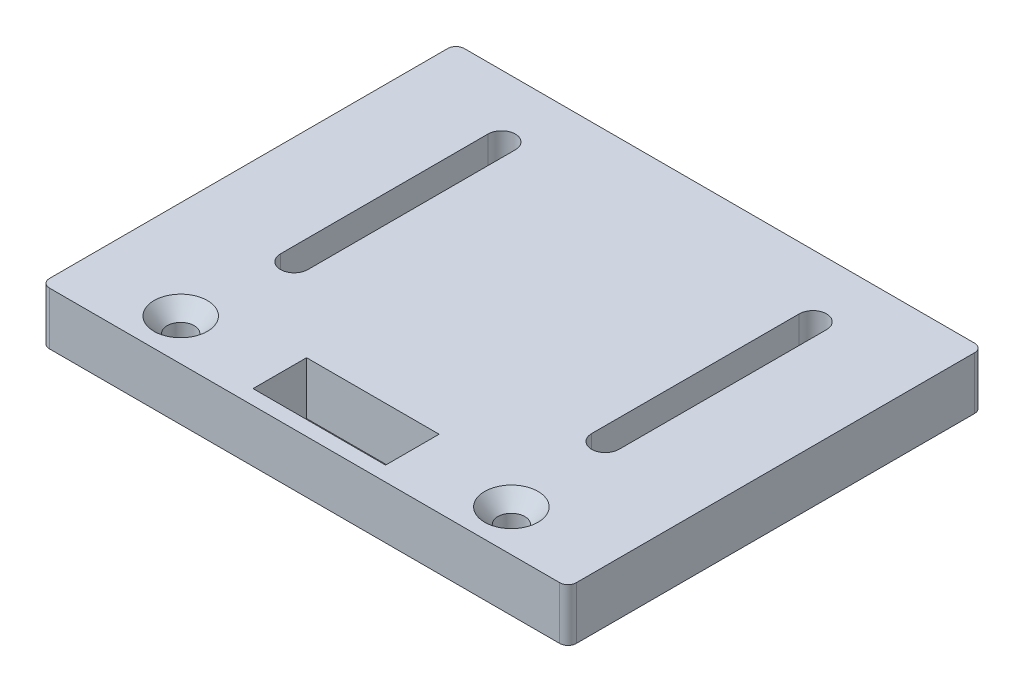
SolidWorks part; units mm, degrees
ref_plane "前基準面" through (0, 0, 0) normal (0, 0, 1) x (1, 0, 0)
ref_plane "上基準面" through (0, 0, 0) normal (0, 1, 0) x (1, 0, 0)
ref_plane "右基準面" through (0, 0, 0) normal (1, 0, 0) x (0, 0, -1)
sketch "Sketch1" plane through (0, 0, 0) normal (0, 1, 0) x (1, 0, 0)
  line L1 (0, 0) -> (127, 0)
  line L2 (0, 0) -> (0, 100)
  line L3 (0, 100) -> (127, 100)
  line L4 (127, 0) -> (127, 100)
extrude "Boss-Extrude1" add sketch "Sketch1" along normal blind 12.7
sketch "Sketch2" plane through (0, 12.7, 0) normal (0, 1, 0) x (1, 0, 0)
  line L6 (47.53, 10) -> (47.53, 16.45)
  line L7 (47.53, 16.45) -> (79.48, 16.45)
  line L8 (79.48, 10) -> (79.48, 16.45)
  line L9 (47.53, 10) -> (47.53, 3.55)
  line L10 (47.53, 3.55) -> (79.48, 3.55)
  line L11 (79.48, 3.55) -> (79.48, 10)
extrude "Cut-Extrude1" cut sketch "Sketch2" against normal blind 12.7
sketch "Sketch4" plane through (0, 12.7, 0) normal (0, 1, 0) x (1, 0, 0)
  point P7 (23.65, 9.9969)
  point P8 (103.35, 9.9969)
sketch "Sketch6" plane through (0, 12.7, 0) normal (0, 1, 0) x (1, 0, 0)
  line L1 (22.7, 35) -> (22.7, 85)
  line L2 (29.3, 35) -> (29.3, 85)
  line L13 (97.7213, 34.9792) -> (97.7517, 84.9792)
  line L14 (104.3213, 34.9752) -> (104.3517, 84.9752)
  arc A6 (22.7, 35) -> (29.3, 35) centre (26, 35) ccw
  arc A11 (29.3, 85) -> (22.7, 85) centre (26, 85) ccw
  arc A12 (97.7517, 84.9792) -> (104.3517, 84.9752) centre (101.0517, 84.9772) cw
  arc A13 (104.3213, 34.9752) -> (97.7213, 34.9792) centre (101.0213, 34.9772) cw
extrude "Cut-Extrude2" cut sketch "Sketch6" against normal through all
fillet "Fillet1" radius 2 4 edges at (127, 6.35, -100) (127, 6.35, 0) (0, 6.35, 0) (0, 6.35, -100)
hole_wizard "CSK for 1/4 Flat Head Machine Screw1" positions "3DSketch1" profile "Sketch7" countersink size "1/4" standard "ANSI Inch" end condition through all
sketch3d "3DSketch1"
  point P0 (23.65, 12.7, -9.9969)
  point P3 (103.35, 12.7, -9.9969)
sketch "Sketch7" plane through (23.65, 12.7, -9.9969) normal (1, 0, 0) x (0, 0, 1)
  line L0 (0, 0) -> (0, 12.7)
  line L1 (0, 12.7) -> (3.2639, 12.7)
  line L2 (3.2639, 12.7) -> (3.2639, 3.6524)
  line L3 (3.2639, 3.6524) -> (6.4389, 0)
  line L5 (6.4389, 0) -> (0, 0)
  line L6 (-3.2639, 3.6524) -> (-6.4389, 0) construction
  line L11 (0, -6.35) -> (0, 107.95) construction
  dimension "Thru Hole Dia." = 6.5278
  dimension "Thru Hole Depth" = 12.7
  dimension "Near C'Sink Dia." = 12.8778
  dimension "Near C'Sink Angle" = 82
sketch "Sketch8" plane through (0, 12.7, 0) normal (0, 1, 0) x (1, 0, 0)
  point P4 (63.505, 10)
